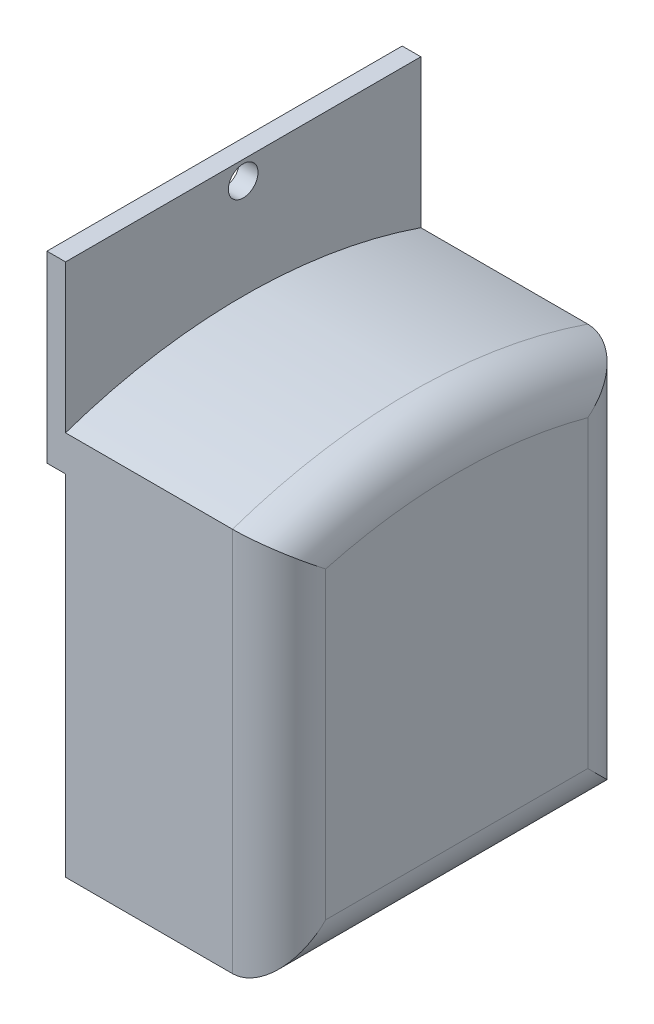
SolidWorks part; units mm, degrees
ref_plane "Front Plane" through (0, 0, 0) normal (0, 0, 1) x (1, 0, 0)
ref_plane "Top Plane" through (0, 0, 0) normal (0, 1, 0) x (1, 0, 0)
ref_plane "Right Plane" through (0, 0, 0) normal (1, 0, 0) x (0, 0, -1)
sketch "Sketch1" plane through (0, 0, 0) normal (0, 0, 1) x (1, 0, 0)
  line L8 (0, 0) -> (0, 49.5132)
  line L9 (0, 76.2) -> (45.8, 76.2)
  line L10 (45.8, 76.2) -> (45.8, 0)
  line L11 (45.8, 0) -> (0, 0)
  line L12 (0, 49.5132) -> (-4, 49.5132)
  line L13 (-4, 49.5132) -> (-4, 88.9)
  line L14 (-4, 88.9) -> (0, 88.9)
  line L15 (0, 88.9) -> (0, 76.2)
  dimension "D1" = 45.8
  dimension "D2" = 76.2
  dimension "D3" = 4
  dimension "D4" = 12.7
extrude "Boss-Extrude1" add sketch "Sketch1" along normal blind 76.2
sketch "Sketch2" plane through (0, 0, 0) normal (1, 0, 0) x (0, 0, -1)
  line L0 (-38.1, 88.9) -> (-38.1, 84.9)
  line L1 (-76.2, 88.9) -> (0, 88.9) construction
  circle A0 centre (-38.1, 84.9) radius 3.175
  dimension "D2" = 6.35
  dimension "D1" = 4
extrude "Cut-Extrude1" cut sketch "Sketch2" against normal blind 76.2 contours A0 region at (0, 82.7184, 40.2816)
sketch "Sketch3" plane through (45.8, 0, 0) normal (1, 0, 0) x (0, 0, -1)
  line L2 (-38.1, 76.2) -> (-38.1, 63.5) construction
  line L3 (-76.2, 76.2) -> (0, 76.2) construction
  line L4 (-38.1, 63.5) -> (-38.1, 57.15)
  line L5 (-76.2, 0) -> (-76.2, 76.2) construction
  line L6 (0, 0) -> (0, 76.2) construction
  line L7 (-76.2, 57.15) -> (-76.2, 76.2)
  line L8 (-76.2, 76.2) -> (0, 76.2)
  line L9 (0, 76.2) -> (0, 57.15)
  arc A2 (-76.2, 57.15) -> (0, 57.15) centre (-38.1, -53.5755) cw
  line M5 (0, 0) -> (0, 76.2)
  line M6 (0, 76.2) -> (-76.2, 76.2)
  line M7 (-76.2, 76.2) -> (-76.2, 0)
  dimension "D1" = 12.7
  dimension "D2" = 6.35
extrude "Cut-Extrude3" cut sketch "Sketch3" against normal blind 45.8 contours L2 A2 M6 M5 | L2 L8 A2 M7 region at (45.8, 68.6896, 17.6889) region at (45.8, 68.6896, 58.5111)
sketch "Sketch4" plane through (0, 0, 76.2) normal (0, 0, 1) x (1, 0, 0)
  line L0 (0, 0) -> (0, -25.4)
  line L1 (45.8, 0) -> (45.8, -25.4)
  line L2 (45.8, -25.4) -> (0, -25.4)
  line L3 (0, 0) -> (45.8, 0)
  dimension "D1" = 25.4
extrude "Boss-Extrude2" add sketch "Sketch4" against normal blind 76.2
fillet "Fillet3" radius 10 4 edges at (45.8, -25.4, 38.1) (45.8, 15.875, 76.2) (45.8, 63.5217, 38.1) (45.8, 15.875, 0)
